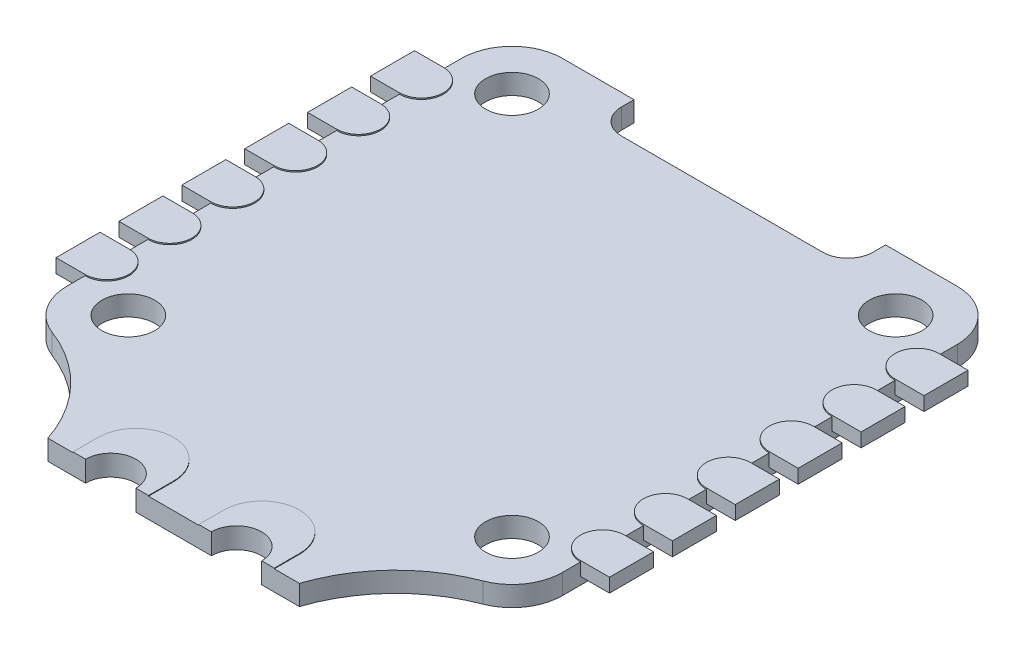
SolidWorks part; units mm, degrees
ref_plane "Front Plane" through (0, 0, 0) normal (0, 0, 1) x (1, 0, 0)
ref_plane "Top Plane" through (0, 0, 0) normal (0, 1, 0) x (1, 0, 0)
ref_plane "Right Plane" through (0, 0, 0) normal (1, 0, 0) x (0, 0, -1)
sketch "Sketch1" plane through (0, 0, 0) normal (0, 1, 0) x (1, 0, 0)
  line L0 (-10, 19.7) -> (-10, 18.7)
  line L1 (-15.7, 19.7) -> (15.7, 19.7)
  line L2 (-19.7, 15.7) -> (-19.7, -15.7)
  line L3 (-15.7, -19.7) -> (15.7, -19.7)
  line L4 (19.7, 15.7) -> (19.7, -15.7)
  line L5 (0, -19.7) -> (0, 19.7) construction
  line L6 (-19.7, 0) -> (19.7, 0) construction
  line L7 (-15.25, 15.25) -> (15.25, 15.25) construction
  line L8 (-15.25, 15.25) -> (-15.25, -15.25) construction
  line L9 (-15.25, -15.25) -> (15.25, -15.25) construction
  line L10 (15.25, 15.25) -> (15.25, -15.25) construction
  line L11 (0, -15.25) -> (0, 15.25) construction
  line L12 (-15.25, 0) -> (15.25, 0) construction
  line L13 (-8, 16.7) -> (8, 16.7)
  line L14 (10, 18.7) -> (10, 19.7)
  line L15 (-10, -19.7) -> (-10, -26.9)
  line L16 (-10, -26.9) -> (10, -26.9)
  line L17 (10, -26.9) -> (10, -19.7)
  line L18 (0, -19.7) -> (0, -26.9) construction
  arc A0 (-19.7, -15.7) -> (-15.7, -19.7) centre (-15.7, -15.7) ccw
  arc A1 (15.7, -19.7) -> (19.7, -15.7) centre (15.7, -15.7) ccw
  arc A2 (19.7, 15.7) -> (15.7, 19.7) centre (15.7, 15.7) ccw
  arc A3 (-15.7, 19.7) -> (-19.7, 15.7) centre (-15.7, 15.7) ccw
  circle A4 centre (-15.25, 15.25) radius 2.1
  circle A5 centre (15.25, 15.25) radius 2.1
  circle A6 centre (15.25, -15.25) radius 2.1
  circle A7 centre (-15.25, -15.25) radius 2.1
  arc A8 (10, 18.7) -> (8, 16.7) centre (8, 18.7) cw
  arc A9 (-8, 16.7) -> (-10, 18.7) centre (-8, 18.7) cw
  arc A10 (-7, -26.9) -> (-3, -26.9) centre (-5, -26.9) cw
  arc A11 (7, -26.9) -> (3, -26.9) centre (5, -26.9) ccw
  point P0 (0, 0)
  point P13 (0, 0)
  point P23 (0, 16.7)
  point P33 (0, -26.9)
  dimension "D3" = 4
  dimension "D5" = 4.2
  dimension "D8" = 2
  dimension "D11" = 2
  dimension "D2" = 39.4
  dimension "D1" = 39.4
  dimension "D4" = 30.5
  dimension "D6" = 3
  dimension "D7" = 10
  dimension "D9" = 7.2
  dimension "D10" = 5
extrude "Boss-Extrude1" add sketch "Sketch1" along normal mid plane 1.6 contours L13 A9 L0 L1 A3 L2 A0 L3 A1 L4 A2 L14 A8 A7 A6 A5 A4 | L16 L17 L3 L15 region at (0, 0, 0.7457) region at (0, 0, 23.037)
fillet "Fillet1" radius 12 2 edges at (-10, 0, 19.7) (10, 0, 19.7)
sketch "Sketch4" plane through (0, 0.8, 0) normal (0, 1, 0) x (1, 0, 0)
  line L0 (0, -26.9) -> (0, -19.9564) construction
  line L1 (-3, -26.9) -> (3, -26.9) construction
  line L2 (-8, -26.9) -> (-8, -24.9)
  line L4 (-2, -24.9) -> (-2, -26.9)
  line L5 (-5, -21.9) -> (-5, -26.9) construction
  line L6 (-10, -26.9) -> (-7, -26.9) construction
  line L7 (-8, -26.9) -> (-2, -26.9)
  line L8 (5, -21.9) -> (5, -26.9) construction
  line L9 (8, -26.9) -> (2, -26.9)
  line L10 (2, -24.9) -> (2, -26.9)
  line L11 (8, -26.9) -> (8, -24.9)
  line L22 (8, 16.7) -> (-8, 16.7)
  line L23 (-10, 18.7) -> (-10, 19.7)
  line L24 (-10, 19.7) -> (-15.7, 19.7)
  line L25 (-19.7, 15.7) -> (-19.7, -15.7)
  line L26 (-10, -26.9) -> (-7, -26.9)
  line L27 (-3, -26.9) -> (3, -26.9)
  line L28 (7, -26.9) -> (10, -26.9)
  line L29 (19.7, -15.7) -> (19.7, 15.7)
  line L30 (15.7, 19.7) -> (10, 19.7)
  line L31 (10, 19.7) -> (10, 18.7)
  line L32 (8, 16.7) -> (-8, 16.7)
  line L33 (-10, 18.7) -> (-10, 19.7)
  line L34 (-10, 19.7) -> (-15.7, 19.7)
  line L35 (-19.7, 15.7) -> (-19.7, -15.7)
  line L36 (-10, -26.9) -> (-7, -26.9)
  line L37 (-3, -26.9) -> (3, -26.9)
  line L38 (7, -26.9) -> (10, -26.9)
  line L39 (19.7, -15.7) -> (19.7, 15.7)
  line L40 (15.7, 19.7) -> (10, 19.7)
  line L41 (10, 19.7) -> (10, 18.7)
  arc A0 (-8, -24.9) -> (-2, -24.9) centre (-5, -24.9) cw
  arc A1 (8, -24.9) -> (2, -24.9) centre (5, -24.9) ccw
  arc A12 (-10, 18.7) -> (-8, 16.7) centre (-8, 18.7) ccw
  arc A13 (-15.7, 19.7) -> (-19.7, 15.7) centre (-15.7, 15.7) ccw
  arc A14 (-19.7, -15.7) -> (-17.1247, -19.4377) centre (-15.7, -15.7) ccw
  arc A15 (-10, -26.9) -> (-17.1247, -19.4377) centre (-21.3988, -30.6507) ccw
  arc A16 (-3, -26.9) -> (-7, -26.9) centre (-5, -26.9) ccw
  arc A17 (7, -26.9) -> (3, -26.9) centre (5, -26.9) ccw
  arc A18 (17.1247, -19.4377) -> (10, -26.9) centre (21.3988, -30.6507) ccw
  arc A19 (17.1247, -19.4377) -> (19.7, -15.7) centre (15.7, -15.7) ccw
  arc A20 (19.7, 15.7) -> (15.7, 19.7) centre (15.7, 15.7) ccw
  arc A21 (8, 16.7) -> (10, 18.7) centre (8, 18.7) ccw
  arc A22 (-10, 18.7) -> (-8, 16.7) centre (-8, 18.7) ccw
  arc A23 (-15.7, 19.7) -> (-19.7, 15.7) centre (-15.7, 15.7) ccw
  arc A24 (-19.7, -15.7) -> (-17.1247, -19.4377) centre (-15.7, -15.7) ccw
  arc A25 (-10, -26.9) -> (-17.1247, -19.4377) centre (-21.3988, -30.6507) ccw
  arc A26 (-3, -26.9) -> (-7, -26.9) centre (-5, -26.9) ccw
  arc A27 (7, -26.9) -> (3, -26.9) centre (5, -26.9) ccw
  arc A28 (17.1247, -19.4377) -> (10, -26.9) centre (21.3988, -30.6507) ccw
  arc A29 (17.1247, -19.4377) -> (19.7, -15.7) centre (15.7, -15.7) ccw
  arc A30 (19.7, 15.7) -> (15.7, 19.7) centre (15.7, 15.7) ccw
  arc A31 (8, 16.7) -> (10, 18.7) centre (8, 18.7) ccw
  line M38 (-10, -26.9) -> (-7, -26.9)
  arc M39 (-7, -26.9) -> (-3, -26.9) centre (-5, -26.9) cw
  line M40 (-3, -26.9) -> (3, -26.9)
  arc M41 (3, -26.9) -> (7, -26.9) centre (5, -26.9) cw
  line M42 (7, -26.9) -> (10, -26.9)
  dimension "D1" = 3
  dimension "D2" = 5
  dimension "D3" = 0
extrude "Boss-Extrude3" add sketch "Sketch4" along normal mid plane 0.1 contours A0 L2 L4 M38 M39 M40 | L11 A1 L10 M40 M41 M42 region at (-5, 0.8, 24.2335) region at (5, 0.8, 24.2335)
sketch "Sketch5" plane through (0, 0.8, 0) normal (0, 1, 0) x (1, 0, 0)
  line L0 (0, 0) -> (0, 16.7) construction
  line L1 (-8, 16.7) -> (8, 16.7) construction
  line L2 (0, 0) -> (-19.7, 0) construction
  line L3 (-19.7, 15.7) -> (-19.7, -15.7) construction
  line L4 (-19.7, 4.25) -> (-22, 4.25)
  line L5 (-22, 4.25) -> (-22, 0.75)
  line L6 (-22, 0.75) -> (-19.7, 0.75)
  line L7 (-22, 5.75) -> (-19.7, 5.75)
  line L8 (-22, 9.25) -> (-22, 5.75)
  line L9 (-19.7, 9.25) -> (-22, 9.25)
  line L10 (-22, 10.75) -> (-19.7, 10.75)
  line L11 (-22, 14.25) -> (-22, 10.75)
  line L12 (-19.7, 14.25) -> (-22, 14.25)
  line L13 (-22, 0.75) -> (-22, 5.75) construction
  line L14 (-22, -0.75) -> (-22, -5.75) construction
  line L15 (-19.7, -14.25) -> (-22, -14.25)
  line L16 (-22, -14.25) -> (-22, -10.75)
  line L17 (-22, -10.75) -> (-19.7, -10.75)
  line L18 (-19.7, -9.25) -> (-22, -9.25)
  line L19 (-22, -9.25) -> (-22, -5.75)
  line L20 (-22, -5.75) -> (-19.7, -5.75)
  line L21 (-22, -0.75) -> (-19.7, -0.75)
  line L22 (-22, -4.25) -> (-22, -0.75)
  line L23 (-19.7, -4.25) -> (-22, -4.25)
  line L24 (22, -0.75) -> (22, -5.75) construction
  line L25 (22, 0.75) -> (22, 5.75) construction
  line L26 (19.7, -4.25) -> (22, -4.25)
  line L27 (22, -4.25) -> (22, -0.75)
  line L28 (22, -0.75) -> (19.7, -0.75)
  line L29 (22, -5.75) -> (19.7, -5.75)
  line L30 (22, -9.25) -> (22, -5.75)
  line L31 (19.7, -9.25) -> (22, -9.25)
  line L32 (22, -10.75) -> (19.7, -10.75)
  line L33 (22, -14.25) -> (22, -10.75)
  line L34 (19.7, -14.25) -> (22, -14.25)
  line L35 (19.7, 14.25) -> (22, 14.25)
  line L36 (22, 14.25) -> (22, 10.75)
  line L37 (22, 10.75) -> (19.7, 10.75)
  line L38 (19.7, 9.25) -> (22, 9.25)
  line L39 (22, 9.25) -> (22, 5.75)
  line L40 (22, 5.75) -> (19.7, 5.75)
  line L41 (22, 0.75) -> (19.7, 0.75)
  line L42 (22, 4.25) -> (22, 0.75)
  line L43 (19.7, 4.25) -> (22, 4.25)
  circle A0 centre (-19.7, 2.5) radius 1.75
  circle A1 centre (-19.7, 7.5) radius 1.75
  circle A2 centre (-19.7, 12.5) radius 1.75
  circle A3 centre (-19.7, -12.5) radius 1.75
  circle A4 centre (-19.7, -7.5) radius 1.75
  circle A5 centre (-19.7, -2.5) radius 1.75
  circle A6 centre (19.7, -2.5) radius 1.75
  circle A7 centre (19.7, -7.5) radius 1.75
  circle A8 centre (19.7, -12.5) radius 1.75
  circle A9 centre (19.7, 12.5) radius 1.75
  circle A10 centre (19.7, 7.5) radius 1.75
  circle A11 centre (19.7, 2.5) radius 1.75
  line M13 (19.7, -15.7) -> (19.7, 15.7)
  line M23 (-19.7, 15.7) -> (-19.7, -15.7)
  dimension "D2" = 3.5
  dimension "D1" = 22
  dimension "D3" = 2.5
  dimension "D5" = 5
  dimension "D4" = 3
extrude "Boss-Extrude4" add sketch "Sketch5" along normal blind 0.1 and the other way blind 1 contours A3 M23 | A3 M23 | L15 A3 L17 L16 | A4 M23 | A4 M23 | L18 A4 L20 L19 | A5 M23 | A5 M23 | L23 A5 L21 L22 | A0 M23 | A0 M23 | A0 L4 L5 L6 | A1 M23 | A1 M23 | A1 L9 L8 L7 | A2 M23 | A2 L12 L11 L10 | A2 M23 | A8 M13 | A8 M13 | A8 L34 L33 L32 | A7 L31 L30 L29 | A7 M13 | A7 M13 | A6 M13 | A6 M13 | A6 L26 L27 L28 | A11 M13 | L43 A11 L41 L42 | A11 M13 | A10 M13 | L38 A10 L40 L39 | A10 M13 | A9 M13 | A9 M13 | L35 A9 L37 L36 region at (-21.4548, 0.8, -2.5) region at (-18.9573, 0.8, 12.5) region at (-20.4427, 0.8, 12.5) region at (-21.4548, 0.8, 12.5) region at (-18.9573, 0.8, 7.5) region at (-20.4427, 0.8, 7.5) region at (-21.4548, 0.8, 7.5) region at (-18.9573, 0.8, 2.5) region at (-20.4427, 0.8, 2.5) region at (-21.4548, 0.8, 2.5) region at (-20.4427, 0.8, -2.5) region at (-21.4548, 0.8, -12.5) region at (-20.4427, 0.8, -12.5) region at (-18.9573, 0.8, -12.5) region at (-21.4548, 0.8, -7.5) region at (-20.4427, 0.8, -7.5) region at (-18.9573, 0.8, -7.5) region at (-18.9573, 0.8, -2.5) region at (21.4548, 0.8, 2.5) region at (18.9573, 0.8, -12.5) region at (20.4427, 0.8, -12.5) region at (21.4548, 0.8, -12.5) region at (18.9573, 0.8, -7.5) region at (20.4427, 0.8, -7.5) region at (21.4548, 0.8, -7.5) region at (18.9573, 0.8, -2.5) region at (20.4427, 0.8, -2.5) region at (21.4548, 0.8, -2.5) region at (20.4427, 0.8, 2.5) region at (21.4548, 0.8, 12.5) region at (20.4427, 0.8, 12.5) region at (18.9573, 0.8, 12.5) region at (21.4548, 0.8, 7.5) region at (20.4427, 0.8, 7.5) region at (18.9573, 0.8, 7.5) region at (18.9573, 0.8, 2.5)
equation "\"D1@Sketch1\"=\"D2@Sketch1\""
